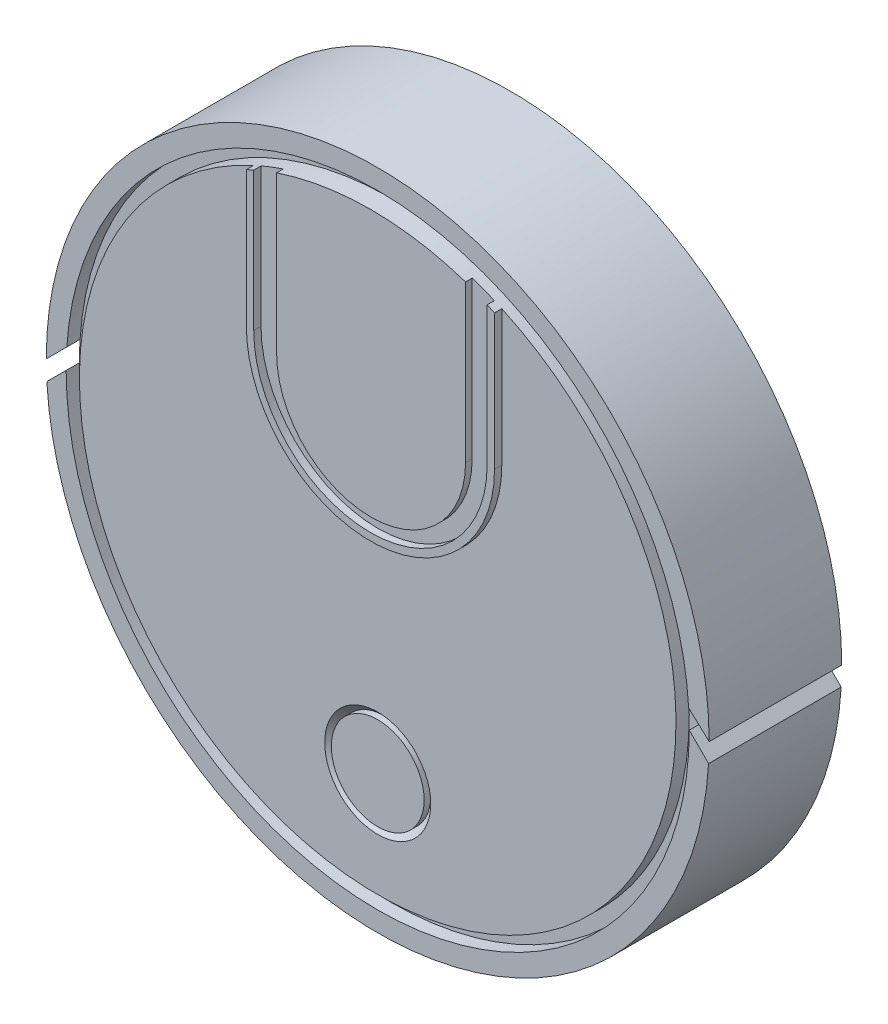
SolidWorks part; units mm, degrees
ref_plane "Front Plane" through (0, 0, 0) normal (0, 0, 1) x (1, 0, 0)
ref_plane "Top Plane" through (0, 0, 0) normal (0, 1, 0) x (1, 0, 0)
ref_plane "Right Plane" through (0, 0, 0) normal (1, 0, 0) x (0, 0, -1)
sketch "Sketch1" plane through (0, 0, 0) normal (0, 0, 1) x (1, 0, 0)
  line L0 (47, 0) -> (49.915, -2.915)
  line L1 (50, 0) -> (46.9134, 2.8516)
  line L2 (-47, 0) -> (-49.915, -2.915)
  line L3 (-50, 0) -> (-46.8975, 3.1025)
  arc A0 (-49.915, -2.915) -> (49.915, -2.915) centre (0, 0) ccw
  arc A1 (-47, 0) -> (47, 0) centre (0, 0) ccw
  arc A2 (50, 0) -> (-50, 0) centre (0, 0) ccw
  arc A3 (46.9134, 2.8516) -> (-46.8975, 3.1025) centre (0, 0) ccw
extrude "Boss-Extrude1" add sketch "Sketch1" along normal blind 20
sketch "Sketch2" plane through (0, 0, 0) normal (0, 0, 1) x (1, 0, 0)
  circle A0 centre (0, 0) radius 47
extrude "Boss-Extrude2" add sketch "Sketch2" along normal blind 18
sketch "Sketch3" plane through (0, 0, 18) normal (0, 0, 1) x (1, 0, 0)
  circle A0 centre (0, 0) radius 45
extrude "Boss-Extrude3" add sketch "Sketch3" along normal blind 2
sketch "Sketch4" plane through (0, 0, 20) normal (0, 0, 1) x (1, 0, 0)
  circle A0 centre (0, -29.1284) radius 7
extrude "Cut-Extrude1" cut sketch "Sketch4" against normal blind 1
chamfer "Chamfer1" distance 1 1 edges at (7, -29.1284, 20)
sketch "Sketch5" plane through (0, 0, 19) normal (0, 0, 1) x (1, 0, 0)
  circle A0 centre (0, -29.1284) radius 7
extrude "Boss-Extrude4" add sketch "Sketch5" along normal blind 1
sketch "Sketch7" plane through (0, 0, 20) normal (0, 0, 1) x (1, 0, 0)
  line L0 (0, 45) -> (0, 19.0697) construction
  line L1 (14.2499, 42.6842) -> (14.2499, 19.0697)
  line L2 (-14.2499, 42.6842) -> (-14.2499, 19.0697)
  circle A0 centre (0, 0) radius 45 construction
  circle A1 centre (0, 0) radius 45 construction
  arc A3 (-14.2499, 19.0697) -> (14.2499, 19.0697) centre (0, 19.0697) ccw
  arc A4 (-14.2499, 42.6842) -> (14.2499, 42.6842) centre (0, 0) cw
  point P7 (0, 45)
extrude "Boss-Extrude5" add sketch "Sketch7" along normal blind 1
sketch "Sketch8" plane through (0, 0, 21) normal (0, 0, 1) x (1, 0, 0)
  line L1 (18.7204, 40.9212) -> (18.7204, 20.4667)
  line L2 (-18.7204, 40.9212) -> (-18.7204, 20.4667)
  line L4 (17.6028, 41.4143) -> (17.6028, 20.4667)
  line L5 (-17.6028, 41.4143) -> (-17.6028, 20.4667)
  arc A0 (14.2499, 42.6842) -> (-14.2499, 42.6842) centre (0, 0) ccw construction
  arc A2 (-18.7204, 20.4667) -> (18.7204, 20.4667) centre (0, 20.4667) ccw
  arc A4 (-17.6028, 20.4667) -> (17.6028, 20.4667) centre (0, 20.4667) ccw
  arc A5 (-18.7204, 40.9212) -> (-17.6028, 41.4143) centre (0, 0) cw
  arc A6 (-14.2499, 42.6842) -> (14.2499, 42.6842) centre (0, 0) ccw construction
  arc A7 (17.6028, 41.4143) -> (18.7204, 40.9212) centre (0, 0) cw
  point P7 (0, 45)
  point P13 (0, 32.7334)
extrude "Boss-Extrude6" add sketch "Sketch8" along normal blind 0.1 and the other way blind 1
